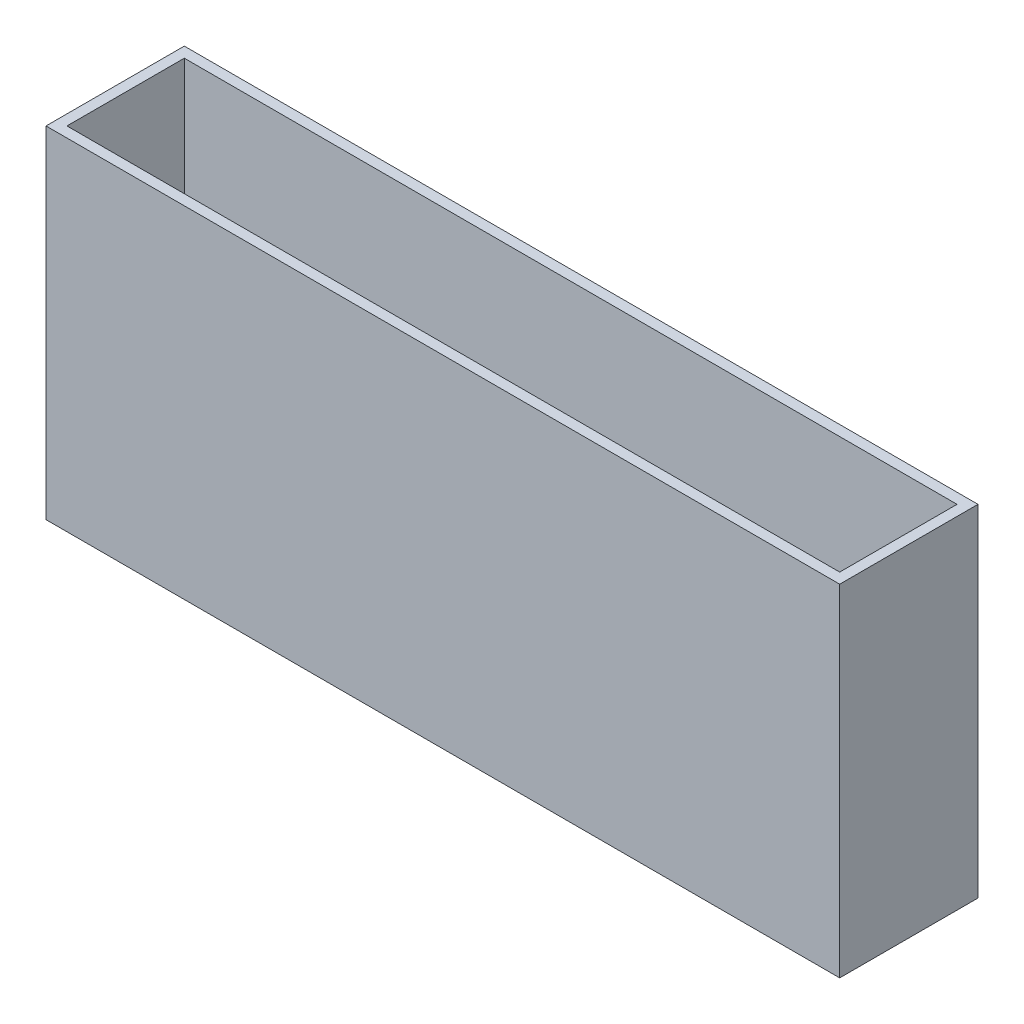
SolidWorks part; units mm, degrees
material "ABS PC"
ref_plane "Front Plane" through (0, 0, 0) normal (0, 0, 1) x (1, 0, 0)
ref_plane "Top Plane" through (0, 0, 0) normal (0, 1, 0) x (1, 0, 0)
ref_plane "Right Plane" through (0, 0, 0) normal (1, 0, 0) x (0, 0, -1)
sketch "Sketch1" plane through (0, 0, 0) normal (0, 1, 0) x (1, 0, 0)
  line L0 (-151.5, -26.4) -> (-151.5, 26.4)
  line L1 (-147.5, -22.4) -> (147.5, -22.4) construction
  line L2 (-147.5, -22.4) -> (-147.5, 22.4) construction
  line L3 (-147.5, 22.4) -> (147.5, 22.4) construction
  line L4 (147.5, -22.4) -> (147.5, 22.4) construction
  line L5 (-147.5, -22.4) -> (147.5, 22.4) construction
  line L6 (-147.5, 22.4) -> (147.5, -22.4) construction
  line L7 (-151.5, 26.4) -> (151.5, 26.4)
  line L8 (151.5, -26.4) -> (151.5, 26.4)
  line L9 (-151.5, -26.4) -> (151.5, -26.4)
  point P0 (0, 0)
  dimension "D1" = 295
  dimension "D2" = 44.8
  dimension "D3" = 4
extrude "Boss-Extrude1" add sketch "Sketch1" along normal blind 3.175
sketch "Sketch2" plane through (0, 3.175, 0) normal (0, 1, 0) x (1, 0, 0)
  line L0 (147.5, 22.4) -> (-147.5, 22.4)
  line L1 (-147.5, 22.4) -> (-147.5, -22.4)
  line L2 (-147.5, -22.4) -> (147.5, -22.4)
  line L3 (147.5, -22.4) -> (147.5, 22.4)
  line L4 (-151.5, -26.4) -> (151.5, -26.4)
  line L5 (151.5, -26.4) -> (151.5, 26.4)
  line L6 (151.5, 26.4) -> (-151.5, 26.4)
  line L7 (-151.5, 26.4) -> (-151.5, -26.4)
  line L8 (-151.5, -26.4) -> (151.5, -26.4)
  line L9 (151.5, -26.4) -> (151.5, 26.4)
  line L10 (151.5, 26.4) -> (-151.5, 26.4)
  line L11 (-151.5, 26.4) -> (-151.5, -26.4)
  dimension "D1" = 0
  dimension "D2" = 4
extrude "Boss-Extrude2" add sketch "Sketch2" along normal blind 127
equation "\"D1@Sketch1\"=7*42mm+1mm"
equation "\"D2@Sketch1\"=10.2mm*4+3mm+1mm"
